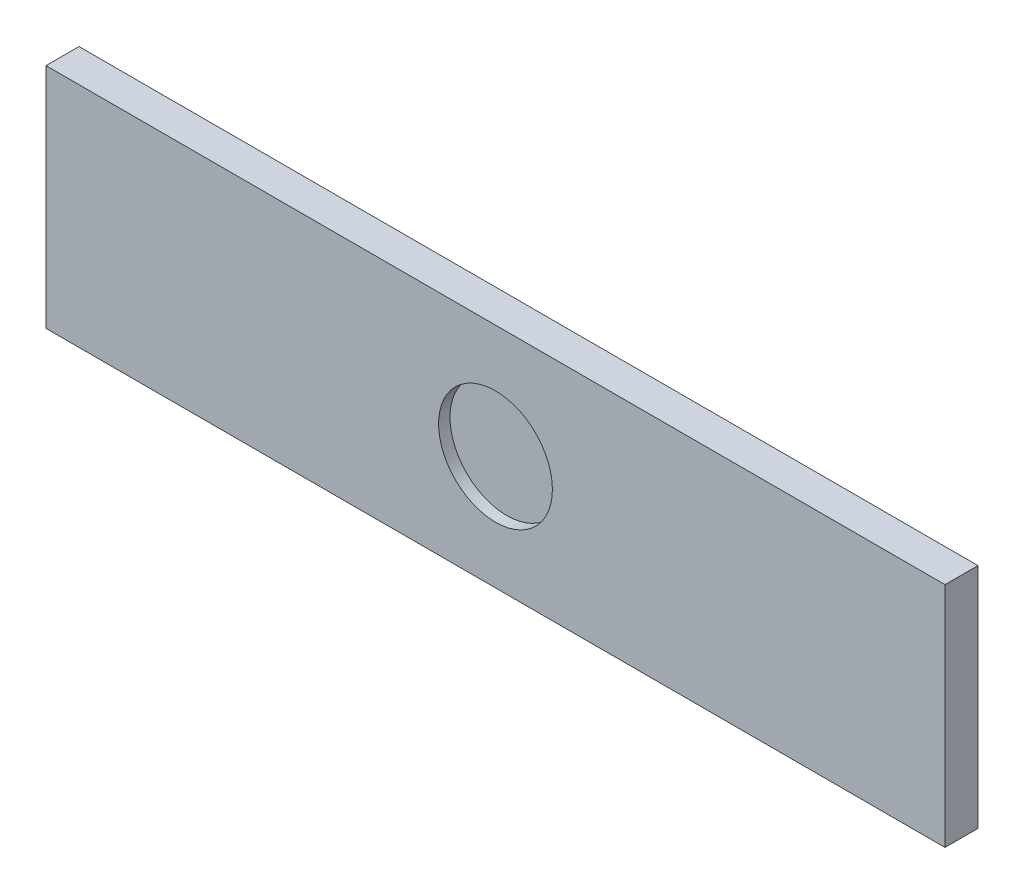
SolidWorks part; units mm, degrees
ref_plane "Front Plane" through (0, 0, 0) normal (0, 0, 1) x (1, 0, 0)
ref_plane "Top Plane" through (0, 0, 0) normal (0, 1, 0) x (1, 0, 0)
ref_plane "Right Plane" through (0, 0, 0) normal (1, 0, 0) x (0, 0, -1)
sketch "Sketch1" plane through (0, 0, 0) normal (0, 0, 1) x (1, 0, 0)
  line L1 (-39.5, 10) -> (39.5, 10)
  line L2 (-39.5, 10) -> (-39.5, -10)
  line L3 (-39.5, -10) -> (39.5, -10)
  line L4 (39.5, 10) -> (39.5, -10)
  line L5 (-39.5, 10) -> (39.5, -10) construction
  line L6 (-39.5, -10) -> (39.5, 10) construction
  point P0 (0, 0)
  dimension "D1" = 79
  dimension "D2" = 20
extrude "Boss-Extrude1" add sketch "Sketch1" along normal blind 2.9
sketch "Sketch2" plane through (0, 0, 2.9) normal (0, 0, 1) x (1, 0, 0)
  circle A0 centre (0, 0) radius 5
  dimension "D1" = 10
extrude "Cut-Extrude1" cut sketch "Sketch2" against normal blind 1
